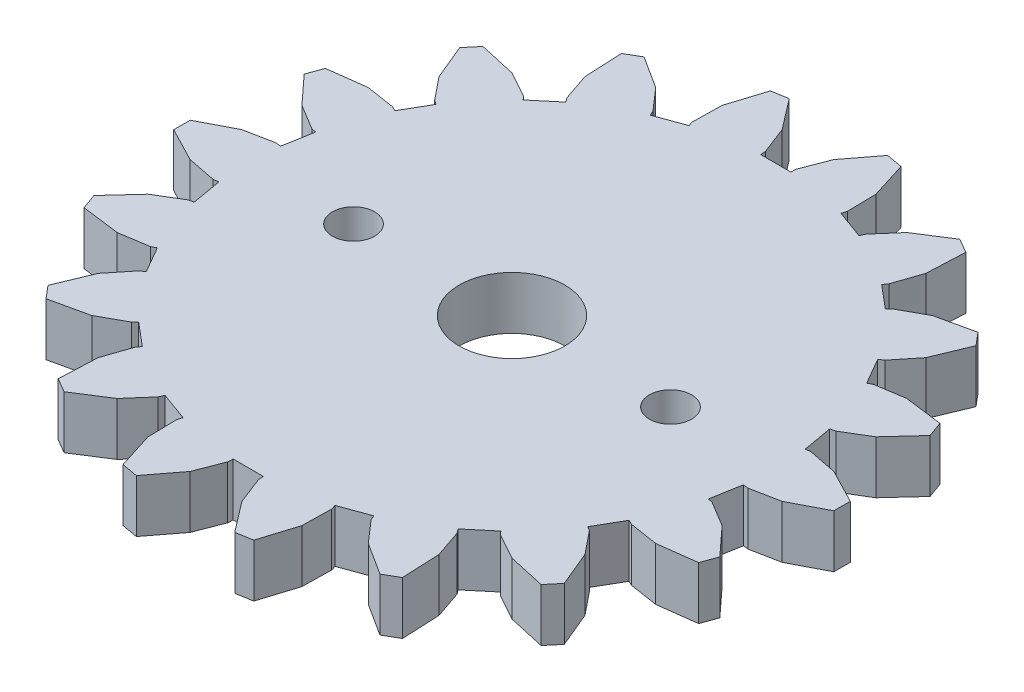
SolidWorks part; units mm, degrees
material "Acrylic (Medium-high impact)"
ref_plane "Front Plane" through (0, 0, 0) normal (0, 0, 1) x (1, 0, 0)
ref_plane "Top Plane" through (0, 0, 0) normal (0, 1, 0) x (1, 0, 0)
ref_plane "Right Plane" through (0, 0, 0) normal (1, 0, 0) x (0, 0, -1)
sketch "Sketch2" plane through (0, 0, 0) normal (0, 1, 0) x (1, 0, 0)
  line L0 (47.7625, 28.9478) -> (48.1516, 28.9935)
  line L1 (48.1516, 28.9935) -> (50.3142, 28.5692)
  line L2 (50.3142, 28.5692) -> (52.8918, 27.2307)
  line L3 (52.8918, 27.2307) -> (52.8918, 25.9859)
  line L4 (52.8918, 25.9859) -> (50.3142, 24.6474)
  line L5 (50.3142, 24.6474) -> (48.1516, 24.2231)
  line L6 (48.1516, 24.2231) -> (47.7625, 24.2688)
  line L7 (47.7625, 24.2688) -> (47.3647, 22.0134)
  line L8 (47.3647, 22.0134) -> (47.7462, 21.9233)
  line L9 (47.7462, 21.9233) -> (49.6331, 20.785)
  line L10 (49.6331, 20.785) -> (51.5977, 18.6455)
  line L11 (51.5977, 18.6455) -> (51.1718, 17.4756)
  line L12 (51.1718, 17.4756) -> (48.2916, 17.0996)
  line L13 (48.2916, 17.0996) -> (46.1145, 17.4405)
  line L14 (46.1145, 17.4405) -> (45.7645, 17.6166)
  line L15 (45.7645, 17.6166) -> (44.6194, 15.6331)
  line L16 (44.6194, 15.6331) -> (44.9469, 15.4181)
  line L17 (44.9469, 15.4181) -> (46.3307, 13.703)
  line L18 (46.3307, 13.703) -> (47.4452, 11.0207)
  line L19 (47.4452, 11.0207) -> (46.6449, 10.0669)
  line L20 (46.6449, 10.0669) -> (43.8096, 10.6987)
  line L21 (43.8096, 10.6987) -> (41.8805, 11.7635)
  line L22 (41.8805, 11.7635) -> (41.6117, 12.0488)
  line L23 (41.6117, 12.0488) -> (39.8572, 10.5766)
  line L24 (39.8572, 10.5766) -> (40.0916, 10.2624)
  line L25 (40.0916, 10.2624) -> (40.8053, 8.1776)
  line L26 (40.8053, 8.1776) -> (40.9351, 5.276)
  line L27 (40.9351, 5.276) -> (39.857, 4.6534)
  line L28 (39.857, 4.6534) -> (37.4087, 6.2167)
  line L29 (37.4087, 6.2167) -> (35.9601, 7.8772)
  line L30 (35.9601, 7.8772) -> (35.8052, 8.2373)
  line L31 (35.8052, 8.2373) -> (33.653, 7.4539)
  line L32 (33.653, 7.4539) -> (33.7657, 7.0785)
  line L33 (33.7657, 7.0785) -> (33.7233, 4.8753)
  line L34 (33.7233, 4.8753) -> (32.8529, 2.1042)
  line L35 (32.8529, 2.1042) -> (31.6267, 1.8881)
  line L36 (31.6267, 1.8881) -> (29.861, 4.1942)
  line L37 (29.861, 4.1942) -> (29.0677, 6.2501)
  line L38 (29.0677, 6.2501) -> (29.0452, 6.6414)
  line L39 (29.0452, 6.6414) -> (26.755, 6.6414)
  line L40 (26.755, 6.6414) -> (26.7324, 6.2501)
  line L41 (26.7324, 6.2501) -> (25.9392, 4.1942)
  line L42 (25.9392, 4.1942) -> (24.1734, 1.8881)
  line L43 (24.1734, 1.8881) -> (22.9472, 2.1042)
  line L44 (22.9472, 2.1042) -> (22.0768, 4.8753)
  line L45 (22.0768, 4.8753) -> (22.0344, 7.0785)
  line L46 (22.0344, 7.0785) -> (22.1471, 7.4539)
  line L47 (22.1471, 7.4539) -> (19.995, 8.2373)
  line L48 (19.995, 8.2373) -> (19.84, 7.8772)
  line L49 (19.84, 7.8772) -> (18.3914, 6.2167)
  line L50 (18.3914, 6.2167) -> (15.9432, 4.6534)
  line L51 (15.9432, 4.6534) -> (14.865, 5.276)
  line L52 (14.865, 5.276) -> (14.9948, 8.1776)
  line L53 (14.9948, 8.1776) -> (15.7085, 10.2624)
  line L54 (15.7085, 10.2624) -> (15.943, 10.5766)
  line L55 (15.943, 10.5766) -> (14.1884, 12.0488)
  line L56 (14.1884, 12.0488) -> (13.9196, 11.7635)
  line L57 (13.9196, 11.7635) -> (11.9905, 10.6987)
  line L58 (11.9905, 10.6987) -> (9.1553, 10.0669)
  line L59 (9.1553, 10.0669) -> (8.355, 11.0207)
  line L60 (8.355, 11.0207) -> (9.4694, 13.703)
  line L61 (9.4694, 13.703) -> (10.8533, 15.4181)
  line L62 (10.8533, 15.4181) -> (11.1808, 15.6331)
  line L63 (11.1808, 15.6331) -> (10.0357, 17.6166)
  line L64 (10.0357, 17.6166) -> (9.6856, 17.4405)
  line L65 (9.6856, 17.4405) -> (7.5085, 17.0996)
  line L66 (7.5085, 17.0996) -> (4.6283, 17.4756)
  line L67 (4.6283, 17.4756) -> (4.2024, 18.6455)
  line L68 (4.2024, 18.6455) -> (6.1671, 20.785)
  line L69 (6.1671, 20.785) -> (8.054, 21.9233)
  line L70 (8.054, 21.9233) -> (8.4355, 22.0134)
  line L71 (8.4355, 22.0134) -> (8.0377, 24.2688)
  line L72 (8.0377, 24.2688) -> (7.6485, 24.2231)
  line L73 (7.6485, 24.2231) -> (5.4859, 24.6474)
  line L74 (5.4859, 24.6474) -> (2.9083, 25.9859)
  line L75 (2.9083, 25.9859) -> (2.9083, 27.2307)
  line L76 (2.9083, 27.2307) -> (5.4859, 28.5692)
  line L77 (5.4859, 28.5692) -> (7.6485, 28.9935)
  line L78 (7.6485, 28.9935) -> (8.0377, 28.9478)
  line L79 (8.0377, 28.9478) -> (8.4355, 31.2032)
  line L80 (8.4355, 31.2032) -> (8.054, 31.2933)
  line L81 (8.054, 31.2933) -> (6.1671, 32.4315)
  line L82 (6.1671, 32.4315) -> (4.2024, 34.5711)
  line L83 (4.2024, 34.5711) -> (4.6283, 35.741)
  line L84 (4.6283, 35.741) -> (7.5085, 36.117)
  line L85 (7.5085, 36.117) -> (9.6856, 35.7761)
  line L86 (9.6856, 35.7761) -> (10.0357, 35.6)
  line L87 (10.0357, 35.6) -> (11.1808, 37.5835)
  line L88 (11.1808, 37.5835) -> (10.8533, 37.7985)
  line L89 (10.8533, 37.7985) -> (9.4694, 39.5136)
  line L90 (9.4694, 39.5136) -> (8.355, 42.1959)
  line L91 (8.355, 42.1959) -> (9.1553, 43.1497)
  line L92 (9.1553, 43.1497) -> (11.9905, 42.5179)
  line L93 (11.9905, 42.5179) -> (13.9196, 41.4531)
  line L94 (13.9196, 41.4531) -> (14.1884, 41.1678)
  line L95 (14.1884, 41.1678) -> (15.943, 42.64)
  line L96 (15.943, 42.64) -> (15.7085, 42.9541)
  line L97 (15.7085, 42.9541) -> (14.9948, 45.0389)
  line L98 (14.9948, 45.0389) -> (14.865, 47.9406)
  line L99 (14.865, 47.9406) -> (15.9432, 48.5632)
  line L100 (15.9432, 48.5632) -> (18.3914, 46.9999)
  line L101 (18.3914, 46.9999) -> (19.84, 45.3394)
  line L102 (19.84, 45.3394) -> (19.995, 44.9793)
  line L103 (19.995, 44.9793) -> (22.1471, 45.7627)
  line L104 (22.1471, 45.7627) -> (22.0344, 46.1381)
  line L105 (22.0344, 46.1381) -> (22.0768, 48.3413)
  line L106 (22.0768, 48.3413) -> (22.9472, 51.1123)
  line L107 (22.9472, 51.1123) -> (24.1734, 51.3285)
  line L108 (24.1734, 51.3285) -> (25.9392, 49.0224)
  line L109 (25.9392, 49.0224) -> (26.7324, 46.9665)
  line L110 (26.7324, 46.9665) -> (26.755, 46.5752)
  line L111 (26.755, 46.5752) -> (29.0452, 46.5752)
  line L112 (29.0452, 46.5752) -> (29.0677, 46.9665)
  line L113 (29.0677, 46.9665) -> (29.861, 49.0224)
  line L114 (29.861, 49.0224) -> (31.6267, 51.3285)
  line L115 (31.6267, 51.3285) -> (32.8529, 51.1123)
  line L116 (32.8529, 51.1123) -> (33.7233, 48.3413)
  line L117 (33.7233, 48.3413) -> (33.7657, 46.1381)
  line L118 (33.7657, 46.1381) -> (33.653, 45.7627)
  line L119 (33.653, 45.7627) -> (35.8052, 44.9793)
  line L120 (35.8052, 44.9793) -> (35.9601, 45.3394)
  line L121 (35.9601, 45.3394) -> (37.4087, 46.9999)
  line L122 (37.4087, 46.9999) -> (39.857, 48.5632)
  line L123 (39.857, 48.5632) -> (40.9351, 47.9406)
  line L124 (40.9351, 47.9406) -> (40.8053, 45.0389)
  line L125 (40.8053, 45.0389) -> (40.0916, 42.9541)
  line L126 (40.0916, 42.9541) -> (39.8572, 42.64)
  line L127 (39.8572, 42.64) -> (41.6117, 41.1678)
  line L128 (41.6117, 41.1678) -> (41.8805, 41.4531)
  line L129 (41.8805, 41.4531) -> (43.8096, 42.5179)
  line L130 (43.8096, 42.5179) -> (46.6449, 43.1497)
  line L131 (46.6449, 43.1497) -> (47.4452, 42.1959)
  line L132 (47.4452, 42.1959) -> (46.3307, 39.5136)
  line L133 (46.3307, 39.5136) -> (44.9469, 37.7985)
  line L134 (44.9469, 37.7985) -> (44.6194, 37.5835)
  line L135 (44.6194, 37.5835) -> (45.7645, 35.6)
  line L136 (45.7645, 35.6) -> (46.1145, 35.7761)
  line L137 (46.1145, 35.7761) -> (48.2916, 36.117)
  line L138 (48.2916, 36.117) -> (51.1718, 35.741)
  line L139 (51.1718, 35.741) -> (51.5977, 34.5711)
  line L140 (51.5977, 34.5711) -> (49.6331, 32.4315)
  line L141 (49.6331, 32.4315) -> (47.7462, 31.2933)
  line L142 (47.7462, 31.2933) -> (47.3647, 31.2032)
  line L143 (47.3647, 31.2032) -> (47.7625, 28.9478)
  line L144 (27.9001, 46.5752) -> (27.9001, 6.6414) construction
  line L145 (52.8918, 26.6083) -> (2.9083, 26.6083) construction
sketch "Sketch3" plane through (0, 0, 0) normal (0, 1, 0) x (1, 0, 0)
  line L0 (27.9001, 46.5752) -> (27.9001, 6.6414) construction
  line L1 (15.9001, 26.6083) -> (39.9001, 26.6083) construction
  line L2 (52.8918, 26.6083) -> (2.9083, 26.6083) construction
  line L3 (27.9001, 32.1459) -> (27.9001, 5.7347) construction
  circle A0 centre (27.9001, 26.6083) radius 4
  circle A1 centre (15.9001, 26.6083) radius 1.6
  circle A2 centre (39.9001, 26.6083) radius 1.6
  point P11 (27.9001, 26.6083)
  dimension "D1" = 8
  dimension "D2" = 3.2
  dimension "D3" = 12
extrude "Boss-Extrude1" add sketch "Sketch2" along normal blind 4
extrude "Cut-Extrude1" cut sketch "Sketch3" along normal up to next
